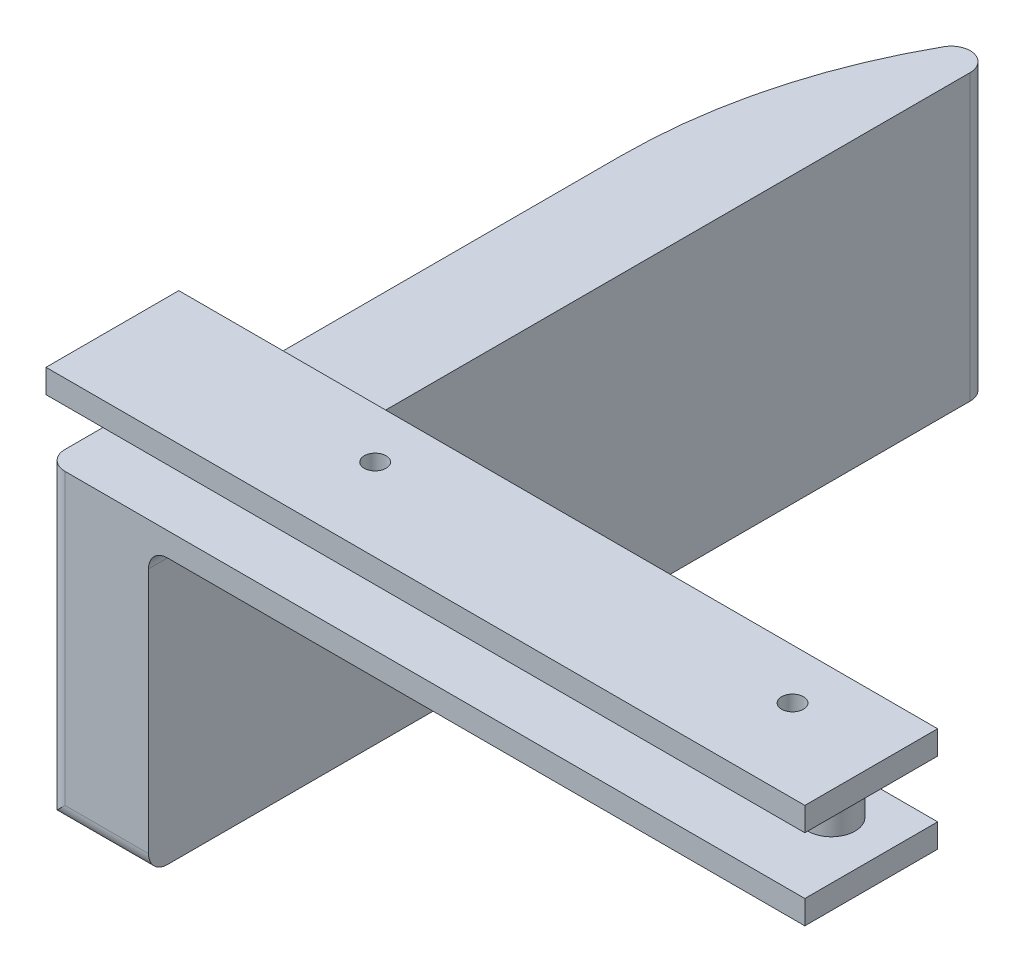
SolidWorks part; units mm, degrees
ref_plane "Front Plane" through (0, 0, 0) normal (0, 0, 1) x (1, 0, 0)
ref_plane "Top Plane" through (0, 0, 0) normal (0, 1, 0) x (1, 0, 0)
ref_plane "Right Plane" through (0, 0, 0) normal (1, 0, 0) x (0, 0, -1)
sketch "Sketch2" plane through (0, 0, 0) normal (0, 1, 0) x (1, 0, 0)
  line L1 (0, 0) -> (101.6, 0)
  line L2 (0, 0) -> (0, 17.78)
  line L3 (0, 17.78) -> (101.6, 17.78)
  line L4 (101.6, 0) -> (101.6, 17.78)
  dimension "D1" = 17.78
  dimension "D2" = 101.6
extrude "Boss-Extrude1" add sketch "Sketch2" along normal blind 3.175
sketch "Sketch3" plane through (0, 0, 0) normal (0, -1, 0) x (1, 0, 0)
  line L0 (93.98, -11.176) -> (5.08, -11.176) construction
  line L1 (93.98, -14.351) -> (5.08, -14.351)
  line L2 (93.98, -8.001) -> (5.08, -8.001)
  line L3 (0, 0) -> (101.6, 0) construction
  line L4 (0, -17.78) -> (0, 0) construction
  arc A0 (93.98, -14.351) -> (93.98, -8.001) centre (93.98, -11.176) ccw
  arc A1 (5.08, -8.001) -> (5.08, -14.351) centre (5.08, -11.176) ccw
  point P2 (49.53, -11.176)
  dimension "D1" = 88.9
  dimension "D2" = 11.176
  dimension "D3" = 5.08
  dimension "D4" = 6.35
extrude "Boss-Extrude2" add sketch "Sketch3" along normal blind 7.62 contours L2 A1 L1 A0
ref_plane "Plane1" through (0, -3.81, 0) normal (0, -1, 0) x (-1, 0, 0)
mirror "Mirror1" about plane through (0, -3.81, 0) normal (0, -1, 0) of "Boss-Extrude1"
sketch "Sketch5" plane through (0, -10.795, 0) normal (0, -1, 0) x (1, 0, 0)
  line L31 (0, 0) -> (13.7244, 0)
  line L32 (0, 0) -> (0, -76.9173)
  line L36 (13.7244, 0) -> (13.7244, -118.618)
  arc A2 (0, -76.9173) -> (13.7244, -118.618) centre (70.2144, -76.9173) ccw
  dimension "D1" = 118.618
extrude "Boss-Extrude3" add sketch "Sketch5" along normal blind 38.1
fillet "Fillet2" radius 2.54 1 edges at (13.7244, -29.845, -118.618)
fillet "Fillet3" radius 2.54 3 edges at (13.7244, -10.795, -8.89) (0, -28.2575, 0) (6.8622, -48.895, 0)
sketch "Sketch6" plane through (0, 3.175, 0) normal (0, 1, 0) x (1, 0, 0)
  line L0 (101.6, 17.78) -> (0, 17.78) construction
  line L1 (101.6, 0) -> (101.6, 17.78) construction
  circle A0 centre (88.9, 11.049) radius 1.4605
  circle A1 centre (33.02, 11.049) radius 1.4605
  dimension "D1" = 2.921
  dimension "D2" = 2.921
  dimension "D3" = 6.731
  dimension "D4" = 6.731
  dimension "D5" = 12.7
  dimension "D6" = 55.88
extrude "Cut-Extrude1" cut sketch "Sketch6" against normal through all
